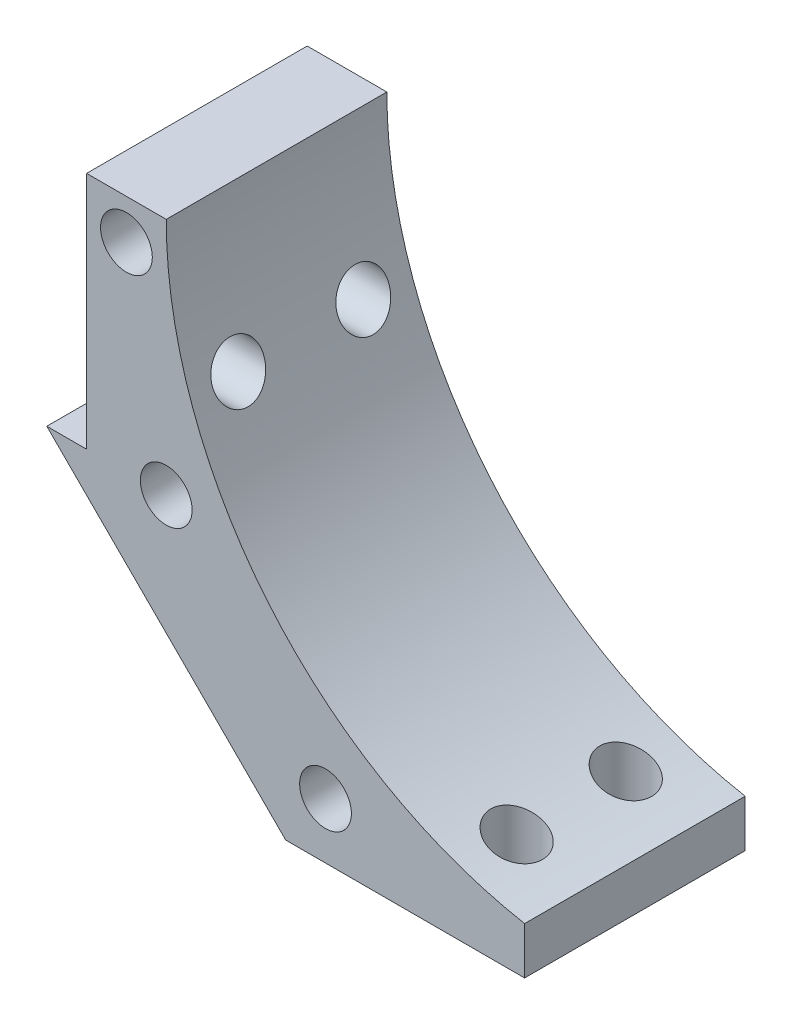
SolidWorks part; units mm, degrees
ref_plane "前视基准面" through (0, 0, 0) normal (0, 0, 1) x (1, 0, 0)
ref_plane "上视基准面" through (0, 0, 0) normal (0, 1, 0) x (1, 0, 0)
ref_plane "右视基准面" through (0, 0, 0) normal (1, 0, 0) x (0, 0, -1)
other "Configuration Table"
sketch "草图1" plane through (0, 0, 0) normal (0, 0, 1) x (1, 0, 0)
  line L0 (0, 30) -> (30, 0)
  line L1 (0, 0) -> (30, 0)
  line L2 (0, 0) -> (0, 30)
  line L3 (0, 30) -> (30, 30)
  line L4 (30, 0) -> (30, 30)
  line L6 (30, 30) -> (60, 30)
  line L7 (30, 30) -> (30, 0)
  line L8 (30, 0) -> (60, 0)
  line L9 (60, 30) -> (60, 0)
  line L10 (5, 30) -> (30, 30)
  line L11 (5, 30) -> (5, 60)
  line L12 (5, 60) -> (30, 60)
  line L13 (30, 30) -> (30, 60)
  dimension "D1" = 30
  dimension "D2" = 30
  dimension "D3" = 30
  dimension "D4" = 30
  dimension "D5" = 5
extrude "凸台-拉伸1" add sketch "草图1" along normal blind 27.7 contours L0 L4 L3 | L7 L6 L9 L8 | L11 L10 L13 L12 region at (20, 20, 0)
sketch "草图3" plane through (0, 0, 27.7) normal (0, 0, 1) x (1, 0, 0)
  line L0 (30, 0) -> (60, 0) construction
  line L1 (0, 30) -> (0, 105.7176) construction
  line L6 (0, 30) -> (30, 0)
  line L7 (30, 0) -> (60, 0)
  line L8 (60, 0) -> (60, 30)
  line L9 (5, 30) -> (0, 30)
  line L10 (0, 30) -> (30, 0)
  line L11 (30, 0) -> (60, 0)
  line L12 (60, 0) -> (60, 30)
  line L13 (5, 30) -> (0, 30)
  line L18 (60, 30) -> (30, 30)
  line L19 (60, 30) -> (30, 30)
  line L20 (30, 30) -> (30, 60)
  line L21 (30, 30) -> (30, 60)
  line L22 (30, 60) -> (5, 60)
  line L23 (30, 60) -> (5, 60)
  line L24 (5, 60) -> (5, 30)
  line L25 (5, 60) -> (5, 30)
  circle A0 centre (70, 60) radius 55
  line M4 (5, 30) -> (0, 30)
  dimension "D1" = 110
  dimension "D2" = 60
  dimension "D3" = 70
  dimension "D4" = 0
extrude "切除-拉伸1" cut sketch "草图3" against normal blind 40 contours A0 L12 M4 region at (28.262, 25.2719, 27.7)
sketch "草图4" plane through (0, 0, 27.7) normal (0, 0, 1) x (1, 0, 0)
  line L6 (15, 60) -> (5, 60)
  line L7 (5, 60) -> (5, 30)
  line L8 (5, 30) -> (0, 30)
  line L9 (0, 30) -> (30, 0)
  line L10 (30, 0) -> (60, 0)
  line L11 (60, 0) -> (60, 5.9167)
  line L12 (15, 60) -> (5, 60)
  line L13 (5, 60) -> (5, 30)
  line L14 (5, 30) -> (0, 30)
  line L15 (0, 30) -> (30, 0)
  line L16 (30, 0) -> (60, 0)
  line L17 (60, 0) -> (60, 5.9167)
  arc A1 (15, 60) -> (60, 5.9167) centre (70, 60) ccw
  arc A2 (15, 60) -> (60, 5.9167) centre (70, 60) ccw
  circle A3 centre (35, 7) radius 3.25
  circle A4 centre (10, 55) radius 3.25
  circle A5 centre (15, 30) radius 3.25
  point P0 (37.225, 2.9217)
  point P16 (67.7811, 24.8219)
  dimension "D2" = 6.5
  dimension "D3" = 30
  dimension "D4" = 6.5
  dimension "D5" = 6.5
  dimension "D9" = 25
  dimension "D10" = 7
  dimension "D6" = 5
  dimension "D7" = 5
  dimension "D8" = 10
  dimension "D1" = 0
extrude "切除-拉伸2" cut sketch "草图4" against normal through all contours A4 | A5 | A3
sketch "草图5" plane through (5, 0, 0) normal (-1, 0, 0) x (0, 0, 1)
  line L0 (27.7, 30) -> (0, 30) construction
  line L1 (27.7, 30) -> (27.7, 60) construction
  line L2 (0, 30) -> (0, 60) construction
  circle A0 centre (6, 42) radius 3.25
  circle A1 centre (21.7, 42) radius 3.25
  dimension "D1" = 6.5
  dimension "D2" = 6.5
  dimension "D3" = 12
  dimension "D4" = 12
  dimension "D5" = 6
  dimension "D6" = 6
extrude "切除-拉伸3" cut sketch "草图5" against normal through all
sketch "草图6" plane through (0, 0, 0) normal (0, -1, 0) x (1, 0, 0)
  line L0 (60, 27.7) -> (60, 0) construction
  line L1 (30, 27.7) -> (60, 27.7) construction
  line L2 (30, 0) -> (60, 0) construction
  circle A0 centre (52, 20.7) radius 3.25
  circle A1 centre (52, 7) radius 3.25
  dimension "D3" = 6.5
  dimension "D4" = 6.5
  dimension "D1" = 8
  dimension "D2" = 8
  dimension "D5" = 7
  dimension "D6" = 7
extrude "切除-拉伸4" cut sketch "草图6" against normal through all
